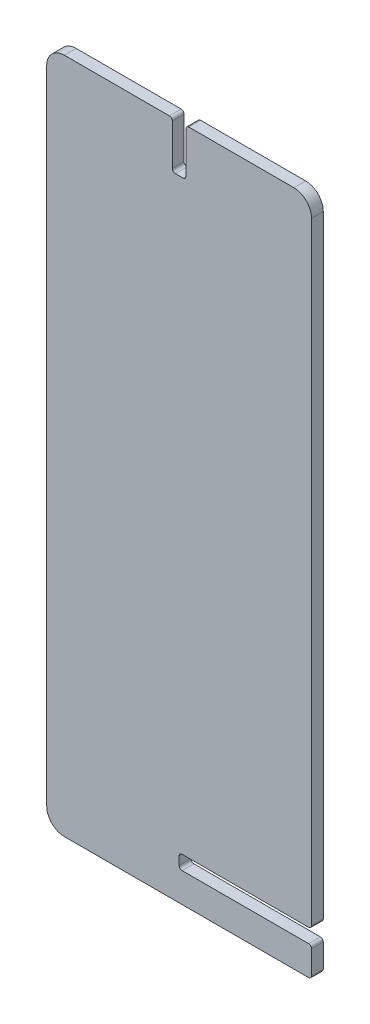
SolidWorks part; units mm, degrees
ref_plane "Alzado" through (0, 0, 0) normal (0, 0, 1) x (1, 0, 0)
ref_plane "Planta" through (0, 0, 0) normal (0, 1, 0) x (1, 0, 0)
ref_plane "Vista lateral" through (0, 0, 0) normal (1, 0, 0) x (0, 0, -1)
sketch "Croquis1" plane through (0, 0, 0) normal (0, 0, 1) x (1, 0, 0)
  line L1 (-22.5, 45) -> (22.5, 45)
  line L2 (-22.5, 45) -> (-22.5, -70)
  line L3 (-22.5, -70) -> (22.5, -70)
  line L4 (22.5, 45) -> (22.5, -70)
  dimension "D1" = 45
  dimension "D2" = 22.5
  dimension "D3" = 115
  dimension "D4" = 45
extrude "Saliente-Extruir1" add sketch "Croquis1" along normal blind 2 contours L2 L3 L4 L1
sketch "Croquis3" plane through (0, 0, 2) normal (0, 0, 1) x (1, 0, 0)
  line L0 (22.5, 45) -> (22.5, -70) construction
  line L1 (22.5, -62.6) -> (0, -62.6)
  line L2 (22.5, -62.6) -> (22.5, -65)
  line L3 (22.5, -65) -> (0, -65)
  line L4 (0, -62.6) -> (0, -65)
  line L5 (-22.5, -70) -> (22.5, -70) construction
  dimension "D1" = 2.4
  dimension "D2" = 5
  dimension "D3" = 22.5
extrude "Cortar-Extruir2" cut sketch "Croquis3" against normal up to surface (2 mm away) up to face at (0, -12.5, 0)
fillet "Redondeo1" radius 3 3 edges at (-22.5, -70, 1) (22.5, 45, 1) (-22.5, 45, 1)
sketch "Croquis4" plane through (0, 0, 2) normal (0, 0, 1) x (1, 0, 0)
  line L5 (0, 0) -> (0, 53.685) construction
  line L6 (-19.5, 45) -> (19.5, 45) construction
  line L7 (-1.15, 45) -> (1.15, 45)
  line L8 (-1.15, 45) -> (-1.15, 37)
  line L9 (-1.15, 37) -> (1.15, 37)
  line L10 (1.15, 45) -> (1.15, 37)
  dimension "D1" = 1.15
  dimension "D2" = 1.15
  dimension "D3" = 8
extrude "Cortar-Extruir3" cut sketch "Croquis4" against normal up to surface (2 mm away) up to face at (2.2617, -26.1435, 0)
fillet "Redondeo2" radius 0.5 9 edges at (0, -62.6, 1) (0, -65, 1) (22.5, -70, 1) (22.5, -65, 1) (22.5, -62.6, 1) (-1.15, 37, 1) (1.15, 37, 1) (-1.15, 45, 1) (1.15, 45, 1)
